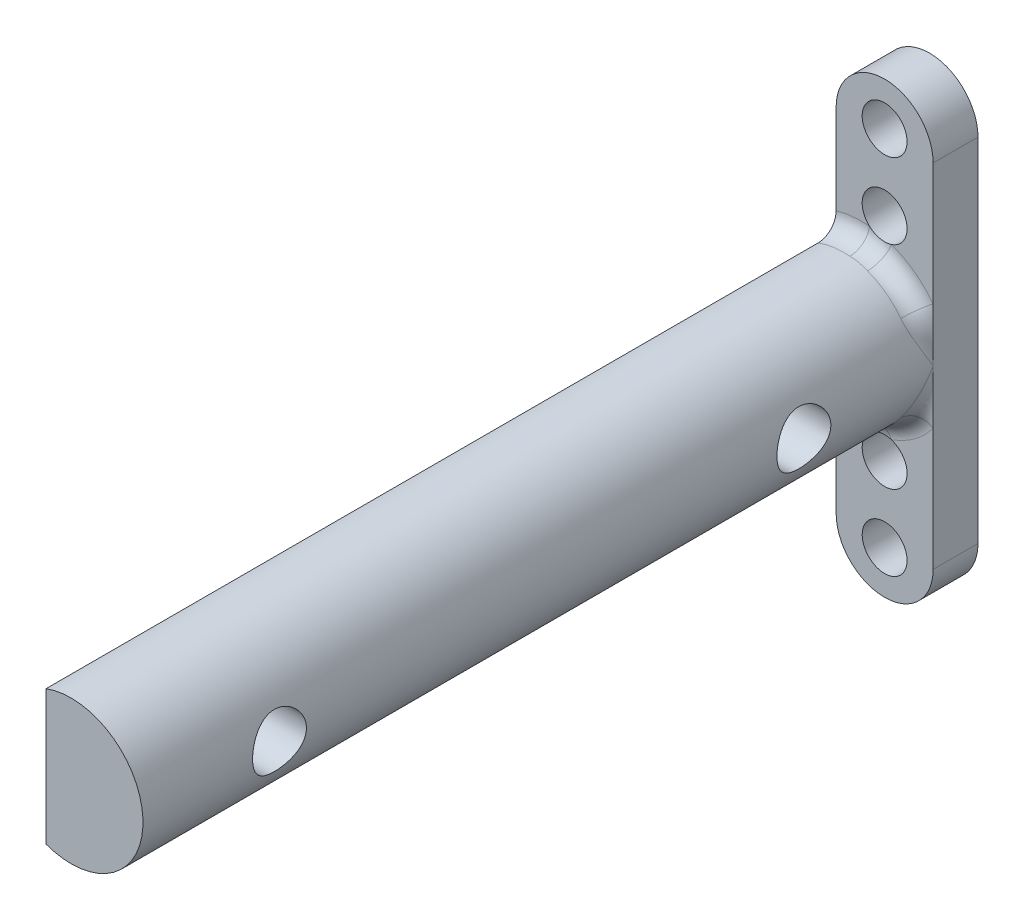
SolidWorks part; units mm, degrees
ref_plane "Front" through (0, 0, 0) normal (0, 0, 1) x (1, 0, 0)
ref_plane "Top" through (0, 0, 0) normal (0, 1, 0) x (1, 0, 0)
ref_plane "Right" through (0, 0, 0) normal (1, 0, 0) x (0, 0, -1)
sketch "Sketch1" plane through (0, 0, 0) normal (0, 0, 1) x (1, 0, 0)
  line L0 (0, 12.446) -> (0, -12.446) construction
  line L1 (3.429, 12.446) -> (3.429, -12.446)
  line L2 (-3.429, 12.446) -> (-3.429, -12.446)
  line L3 (0, 15.875) -> (0, -15.875) construction
  line L4 (-3.429, 0) -> (3.429, 0) construction
  arc A0 (3.429, 12.446) -> (-3.429, 12.446) centre (0, 12.446) ccw
  arc A1 (-3.429, -12.446) -> (3.429, -12.446) centre (0, -12.446) ccw
  circle A2 centre (0, 12.827) radius 1.5875
  circle A3 centre (0, 7.493) radius 1.5875
  circle A4 centre (0, -12.827) radius 1.5875
  circle A5 centre (0, -7.493) radius 1.5875
  point P3 (0, 0)
  dimension "D3" = 3.175
  dimension "D5" = 8.382
  dimension "D1" = 6.858
  dimension "D2" = 31.75
  dimension "D4" = 3.048
extrude "Boss-Extrude1" add sketch "Sketch1" along normal blind 3.175
sketch "Sketch2" plane through (0, 0, 3.175) normal (0, 0, 1) x (1, 0, 0)
  line L0 (3.429, -12.446) -> (3.429, 12.446) construction
  line L1 (-3.429, 4.7587) -> (-3.429, -4.7587)
  line L2 (-3.429, 12.446) -> (-3.429, -12.446) construction
  arc A0 (-3.429, -4.7587) -> (-3.429, 4.7587) centre (-1.651, 0) ccw
  dimension "D1" = 10.16
extrude "Boss-Extrude2" add sketch "Sketch2" along normal blind 55.88
sketch "Sketch3" plane through (-3.429, 0, 0) normal (-1, 0, 0) x (0, 0, 1)
  line L1 (2.6546, 0) -> (12.3128, 0) construction
  line L2 (49.3968, 0) -> (59.055, 0) construction
  line L3 (59.055, 4.7587) -> (59.055, -4.7587) construction
  circle A0 centre (12.3128, 0) radius 1.905
  circle A1 centre (49.3968, 0) radius 1.905
  dimension "D1" = 3.81
  dimension "D2" = 37.084
extrude "Cut-Extrude1" cut sketch "Sketch3" against normal blind 55.88 contours A0 | A1
fillet "Fillet1" radius 1.27 2 edges
